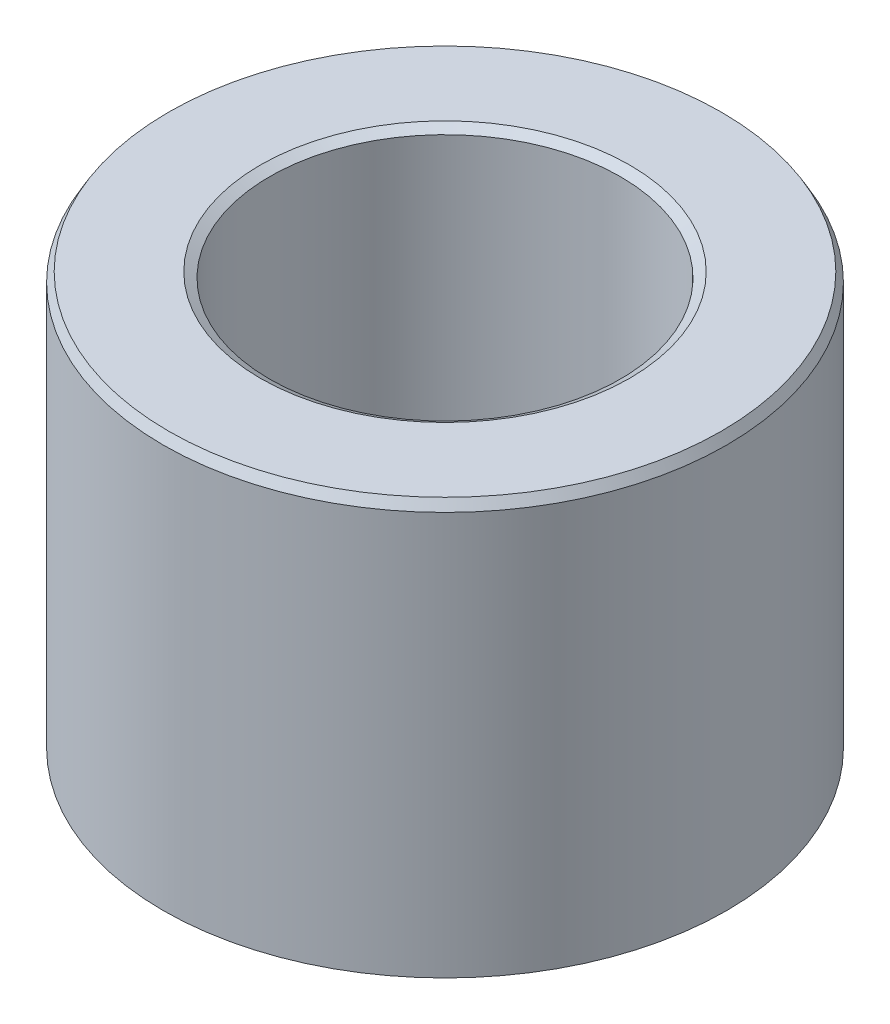
SolidWorks part; units mm, degrees
ref_plane "Front Plane" through (0, 0, 0) normal (0, 0, 1) x (1, 0, 0)
ref_plane "Top Plane" through (0, 0, 0) normal (0, 1, 0) x (1, 0, 0)
ref_plane "Right Plane" through (0, 0, 0) normal (1, 0, 0) x (0, 0, -1)
sketch "Sketch1" plane through (0, 0, 0) normal (0, 1, 0) x (1, 0, 0)
  circle A0 centre (0, 0) radius 47.5
  dimension "SLEEVE_OD" = 95
extrude "Boss-Extrude1" add sketch "Sketch1" along normal blind 70.4505
sketch "Sketch2" plane through (0, 0, 0) normal (0, 1, 0) x (1, 0, 0)
  circle A0 centre (0, 0) radius 29.5714
  dimension "BORE_D" = 59.1429
extrude "Cut-Extrude1" cut sketch "Sketch2" along normal through all
chamfer "Chamfer1" distance 1.5707 angle 30 4 edges at (0, 70.4505, 29.5714) (0, 0, 29.5714) (0, 0, 47.5) (0, 70.4505, 47.5) first distance on face at (0, 70.4505, 29.5714) first distance on face at (0, 0, 29.5714) first distance on face at (0, 70.4505, 47.5)
